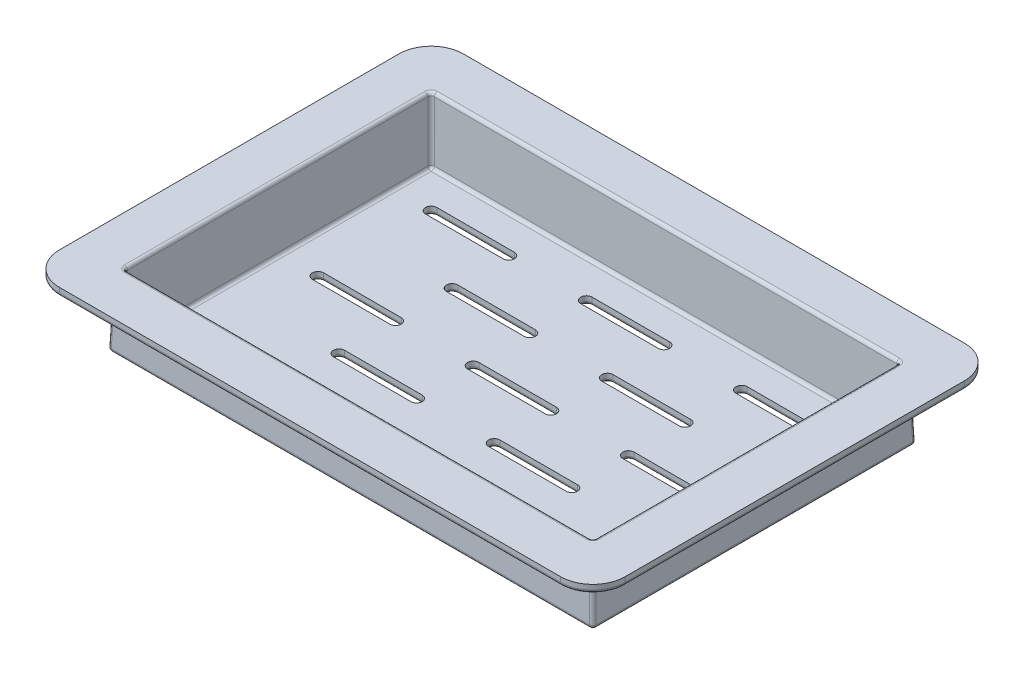
SolidWorks part; units mm, degrees
ref_plane "Front Plane" through (0, 0, 0) normal (0, 0, 1) x (1, 0, 0)
ref_plane "Top Plane" through (0, 0, 0) normal (0, 1, 0) x (1, 0, 0)
ref_plane "Right Plane" through (0, 0, 0) normal (1, 0, 0) x (0, 0, -1)
sketch "Sketch19" plane through (0, 0, 0) normal (0, 1, 0) x (1, 0, 0)
  line L0 (0, 0) -> (0, 49676.8473) construction
  line L1 (0, 0) -> (-49676.8473, 0) construction
  line L3 (87.5, -62.5) -> (-87.5, -62.5)
  line L4 (87.5, -62.5) -> (87.5, 62.5)
  line L5 (87.5, 62.5) -> (-87.5, 62.5)
  line L6 (-87.5, -62.5) -> (-87.5, 62.5)
  line L7 (87.5, -62.5) -> (-87.5, 62.5) construction
  line L8 (87.5, 62.5) -> (-87.5, -62.5) construction
  point P5 (0, 0)
  dimension "D1" = 175
  dimension "D2" = 125
extrude "Boss-Extrude4" add sketch "Sketch19" against normal blind 22
sketch "Sketch20" plane through (0, 0, 0) normal (0, 1, 0) x (1, 0, 0)
  line L1 (72.5, -47.5) -> (-72.5, -47.5)
  line L2 (72.5, -47.5) -> (72.5, 47.5)
  line L3 (72.5, 47.5) -> (-72.5, 47.5)
  line L4 (-72.5, -47.5) -> (-72.5, 47.5)
  line L5 (72.5, -47.5) -> (-72.5, 47.5) construction
  line L6 (72.5, 47.5) -> (-72.5, -47.5) construction
  point P0 (0, 0)
  dimension "D1" = 145
  dimension "D2" = 95
extrude "Cut-Extrude4" cut sketch "Sketch20" against normal blind 19.5 draft 3
sketch "Sketch21" plane through (0, -22, 0) normal (0, -1, 0) x (1, 0, 0)
  line L1 (75.5, -50.5) -> (-75.5, -50.5)
  line L2 (75.5, -50.5) -> (75.5, 50.5)
  line L3 (75.5, 50.5) -> (-75.5, 50.5)
  line L4 (-75.5, -50.5) -> (-75.5, 50.5)
  line L5 (75.5, -50.5) -> (-75.5, 50.5) construction
  line L6 (75.5, 50.5) -> (-75.5, -50.5) construction
  line L7 (87.5, -62.5) -> (-87.5, -62.5)
  line L8 (87.5, -62.5) -> (87.5, 62.5)
  line L9 (87.5, 62.5) -> (-87.5, 62.5)
  line L10 (-87.5, -62.5) -> (-87.5, 62.5)
  line L11 (87.5, -62.5) -> (-87.5, 62.5) construction
  line L12 (87.5, 62.5) -> (-87.5, -62.5) construction
  point P0 (0, 0)
  point P6 (0, 0)
  dimension "D1" = 151
  dimension "D2" = 101
extrude "Cut-Extrude5" cut sketch "Sketch21" against normal blind 19.5
sketch "Sketch26" plane through (0, -22, 0) normal (0, -1, 0) x (1, 0, 0)
  line L4 (-75.5, -50.5) -> (75.5, -50.5) construction
  line L5 (75.5, -50.5) -> (75.5, 50.5) construction
  line L6 (-75.5, 50.5) -> (-75.5, -50.5) construction
  line L7 (75.5, 50.5) -> (-75.5, 50.5) construction
  line L8 (-75, 50) -> (-75, -50)
  line L9 (-75, -50) -> (75, -50)
  line L10 (75, -50) -> (75, 50)
  line L11 (75, 50) -> (-75, 50)
  line L12 (-75, 50) -> (-75, -50)
  line L13 (-75, -50) -> (75, -50)
  line L14 (75, -50) -> (75, 50)
  line L15 (75, 50) -> (-75, 50)
  line L16 (-75.5, -50.5) -> (75.5, -50.5)
  line L17 (75.5, -50.5) -> (75.5, 50.5)
  line L18 (-75.5, 50.5) -> (-75.5, -50.5)
  line L19 (75.5, 50.5) -> (-75.5, 50.5)
  dimension "D1" = 0.5
extrude "Cut-Extrude10" cut sketch "Sketch26" against normal blind 19.5 draft 2 draft outward yes
fillet "Fillet2" radius 1 28 edges at (-71.989, -9.75, 46.989) (71.989, -9.75, 46.989) (71.989, -9.75, -46.989) (-71.989, -9.75, -46.989) (72.5, 0, 0) (0, 0, -47.5) (0, 0, 47.5) (-72.5, 0, 0) (0, -19.5, -46.478) (71.478, -19.5, 0) (0, -19.5, 46.478) (-71.478, -19.5, 0) (74.319, -2.5, 0) (-74.319, -2.5, 0) (74.6595, -12.25, -49.6595) (0, -2.5, -49.319) (-74.6595, -12.25, -49.6595) (75, -22, 0) (0, -22, -50) (-75, -22, 0) (0, -22, 50) (0, -2.5, 49.319) (0, -2.5, 62.5) (87.5, -2.5, 0) (0, -2.5, -62.5) (-87.5, -2.5, 0) (-74.6595, -12.25, 49.6595) (74.6595, -12.25, 49.6595)
fillet "Fillet3" radius 10 8 edges at (-87.5, -0.75, -62.5) (87.5, -0.75, -62.5) (87.5, -0.75, 62.5) (-87.5, -0.75, 62.5) (-87.2071, -2.2071, 62.2071) (87.2071, -2.2071, 62.2071) (87.2071, -2.2071, -62.2071) (-87.2071, -2.2071, -62.2071)
sketch "Sketch27" plane through (0, -22, 0) normal (0, -1, 0) x (1, 0, 0)
  line L0 (0, 0) -> (0, 50000) construction
  line L1 (-12, 0) -> (12, 0) construction
  line L2 (0, 0) -> (-50000, 0) construction
  line L3 (-12, 1.75) -> (12, 1.75)
  line L4 (-12, -1.75) -> (12, -1.75)
  line L5 (36, 0) -> (60, 0) construction
  line L6 (36, 1.75) -> (60, 1.75)
  line L7 (36, -1.75) -> (60, -1.75)
  line L8 (-60, 0) -> (-36, 0) construction
  line L9 (-60, 1.75) -> (-36, 1.75)
  line L10 (-60, -1.75) -> (-36, -1.75)
  line L11 (-36, 17.5) -> (-12, 17.5) construction
  line L12 (-36, 19.25) -> (-12, 19.25)
  line L13 (-36, 15.75) -> (-12, 15.75)
  line L14 (12, 17.5) -> (36, 17.5) construction
  line L15 (12, 19.25) -> (36, 19.25)
  line L16 (12, 15.75) -> (36, 15.75)
  line L17 (12, 35) -> (-12, 35) construction
  line L18 (12, 33.25) -> (-12, 33.25)
  line L19 (12, 36.75) -> (-12, 36.75)
  line L20 (12, -35) -> (-12, -35) construction
  line L21 (12, -33.25) -> (-12, -33.25)
  line L22 (12, -36.75) -> (-12, -36.75)
  line L23 (12, -17.5) -> (36, -17.5) construction
  line L24 (12, -19.25) -> (36, -19.25)
  line L25 (12, -15.75) -> (36, -15.75)
  line L26 (-36, -17.5) -> (-12, -17.5) construction
  line L27 (-36, -19.25) -> (-12, -19.25)
  line L28 (-36, -15.75) -> (-12, -15.75)
  line L29 (0, 17.5) -> (-50000, 17.5) construction
  line L30 (0, -17.5) -> (-50000, -17.5) construction
  line L31 (36, -35) -> (60, -35) construction
  line L32 (36, -36.75) -> (60, -36.75)
  line L33 (36, -33.25) -> (60, -33.25)
  line L34 (-60, -35) -> (-36, -35) construction
  line L35 (-60, -36.75) -> (-36, -36.75)
  line L36 (-60, -33.25) -> (-36, -33.25)
  line L37 (-60, 35) -> (-36, 35) construction
  line L38 (-60, 33.25) -> (-36, 33.25)
  line L39 (-60, 36.75) -> (-36, 36.75)
  line L40 (36, 35) -> (60, 35) construction
  line L41 (36, 33.25) -> (60, 33.25)
  line L42 (36, 36.75) -> (60, 36.75)
  arc A0 (-12, 1.75) -> (-12, -1.75) centre (-12, 0) ccw
  arc A1 (12, -1.75) -> (12, 1.75) centre (12, 0) ccw
  arc A2 (36, 1.75) -> (36, -1.75) centre (36, 0) ccw
  arc A3 (60, -1.75) -> (60, 1.75) centre (60, 0) ccw
  arc A4 (-60, 1.75) -> (-60, -1.75) centre (-60, 0) ccw
  arc A5 (-36, -1.75) -> (-36, 1.75) centre (-36, 0) ccw
  arc A6 (-36, 19.25) -> (-36, 15.75) centre (-36, 17.5) ccw
  arc A7 (-12, 15.75) -> (-12, 19.25) centre (-12, 17.5) ccw
  arc A8 (12, 19.25) -> (12, 15.75) centre (12, 17.5) ccw
  arc A9 (36, 15.75) -> (36, 19.25) centre (36, 17.5) ccw
  arc A10 (12, 33.25) -> (12, 36.75) centre (12, 35) ccw
  arc A11 (-12, 36.75) -> (-12, 33.25) centre (-12, 35) ccw
  arc A12 (12, -33.25) -> (12, -36.75) centre (12, -35) cw
  arc A13 (-12, -36.75) -> (-12, -33.25) centre (-12, -35) cw
  arc A14 (12, -19.25) -> (12, -15.75) centre (12, -17.5) cw
  arc A15 (36, -15.75) -> (36, -19.25) centre (36, -17.5) cw
  arc A16 (-36, -19.25) -> (-36, -15.75) centre (-36, -17.5) cw
  arc A17 (-12, -15.75) -> (-12, -19.25) centre (-12, -17.5) cw
  arc A18 (36, -36.75) -> (36, -33.25) centre (36, -35) cw
  arc A19 (60, -33.25) -> (60, -36.75) centre (60, -35) cw
  arc A20 (-60, -36.75) -> (-60, -33.25) centre (-60, -35) cw
  arc A21 (-36, -33.25) -> (-36, -36.75) centre (-36, -35) cw
  arc A22 (-60, 33.25) -> (-60, 36.75) centre (-60, 35) cw
  arc A23 (-36, 36.75) -> (-36, 33.25) centre (-36, 35) cw
  arc A24 (36, 33.25) -> (36, 36.75) centre (36, 35) cw
  arc A25 (60, 36.75) -> (60, 33.25) centre (60, 35) cw
  point P7 (0, 0)
  point P15 (48, 0)
  point P22 (-48, 0)
  point P28 (-24, 17.5)
  point P35 (24, 17.5)
  point P40 (0, 35)
  point P49 (0, -35)
  point P56 (24, -17.5)
  point P63 (-24, -17.5)
  point P74 (48, -35)
  point P81 (-48, -35)
  point P88 (-48, 35)
  point P95 (48, 35)
  dimension "D1" = 24
  dimension "D2" = 3.5
  dimension "D7" = 24
  dimension "D8" = 35
  dimension "D9" = 24
  dimension "D10" = 3.5
  dimension "D11" = 24
  dimension "D12" = 3.5
  dimension "D13" = 17.5
  dimension "D14" = 17.5
  dimension "D15" = 3.5
  dimension "D3" = 2
  dimension "D5" = 2
extrude "Cut-Extrude11" cut sketch "Sketch27" against normal blind 19.5
fillet "Fillet4" radius 1 52 edges at (48, -22, -33.25) (61.75, -22, -35) (48, -22, -36.75) (0, -22, -33.25) (13.75, -22, -35) (0, -22, -36.75) (-48, -22, -36.75) (-61.75, -22, -35) (-48, -22, -33.25) (24, -22, -15.75) (37.75, -22, -17.5) (24, -22, -19.25) (-24, -22, -19.25) (-37.75, -22, -17.5) (-24, -22, -15.75) (0, -22, -1.75) (-13.75, -22, 0) (0, -22, 1.75) (-48, -22, -1.75) (-61.75, -22, 0) (-48, -22, 1.75) (-24, -22, 15.75) (-37.75, -22, 17.5) (-24, -22, 19.25) (24, -22, 15.75) (10.25, -22, 17.5) (24, -22, 19.25) (48, -22, -1.75) (34.25, -22, 0) (48, -22, 1.75) (48, -22, 33.25) (34.25, -22, 35) (48, -22, 36.75) (0, -22, 33.25) (-13.75, -22, 35) (0, -22, 36.75) (-34.25, -22, 35) (-48, -22, 33.25) (-61.75, -22, 35) (34.25, -22, -35) (-13.75, -22, -35) (-34.25, -22, -35) (10.25, -22, -17.5) (-10.25, -22, -17.5) (13.75, -22, 0) (-34.25, -22, 0) (-10.25, -22, 17.5) (37.75, -22, 17.5) (61.75, -22, 0) (61.75, -22, 35) (13.75, -22, 35) (-48, -22, 36.75)
